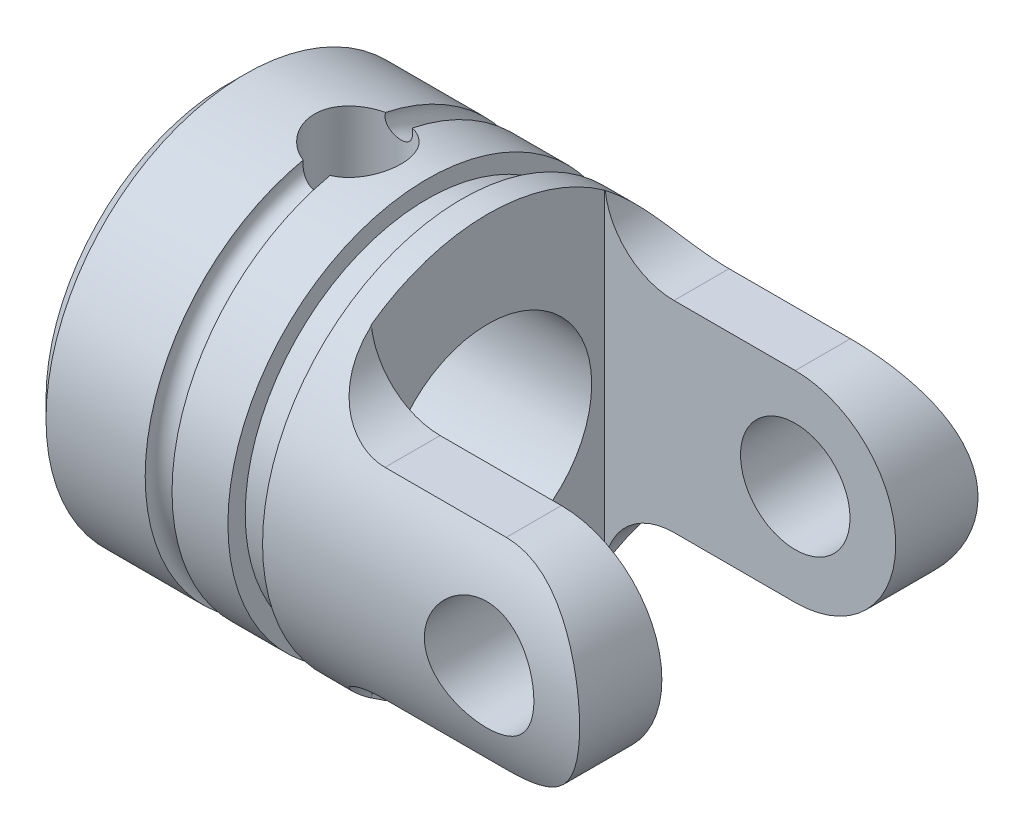
SolidWorks part; units mm, degrees
ref_plane "Front Plane" through (0, 0, 0) normal (0, 0, 1) x (1, 0, 0)
ref_plane "Top Plane" through (0, 0, 0) normal (0, 1, 0) x (1, 0, 0)
ref_plane "Right Plane" through (0, 0, 0) normal (1, 0, 0) x (0, 0, -1)
ref_plane "Plane1" through (0, 0, 0) normal (0, 0, 1) x (1, 0, 0)
sketch "Sketch1" plane through (0, 0, 0) normal (0, 0, 1) x (1, 0, 0)
  line L0 (0, 10.5) -> (0, 7)
  line L1 (0, 7) -> (1, 6)
  line L2 (1, 6) -> (31.8, 6)
  line L3 (31.8, 6) -> (31.8, 11.5)
  line L4 (31.8, 11.5) -> (13.5, 11.5)
  line L5 (13.5, 11.5) -> (13.5, 10.5)
  line L6 (13.5, 10.5) -> (11.5, 10.5)
  line L7 (11.5, 10.5) -> (11.5, 11.5)
  line L8 (11.5, 11.5) -> (8.2746, 11.5)
  line L9 (6.7254, 11.5) -> (1, 11.5)
  line L10 (1, 11.5) -> (0, 10.5)
  line L11 (31.8, 0) -> (0, 0) construction
  arc A0 (8.2746, 11.5) -> (6.7254, 11.5) centre (7.5, 11.3) cw
revolve "Revolve1" add sketch "Sketch1" angle 360 about L11 reverse direction yes
ref_plane "Plane2" through (0, 0, 0) normal (0, 0, 1) x (1, 0, 0)
sketch "Sketch2" plane through (0, 0, 0) normal (0, 0, 1) x (1, 0, 0)
  line L0 (15, 12.5) -> (15, 9.8)
  line L1 (19, 5.8) -> (26, 5.8)
  line L2 (26, -5.8) -> (19, -5.8)
  line L3 (15, -9.8) -> (15, -12.5)
  line L4 (15, -12.5) -> (41, -12.5)
  line L5 (41, -12.5) -> (41, 12.5)
  line L6 (41, 12.5) -> (15, 12.5)
  arc A0 (15, 9.8) -> (19, 5.8) centre (19, 9.8) ccw
  arc A1 (26, 5.8) -> (26, -5.8) centre (26, 0) cw
  arc A2 (19, -5.8) -> (15, -9.8) centre (19, -9.8) ccw
extrude "Cut-Extrude1" cut sketch "Sketch2" against normal blind 23 and the other way blind 23
ref_plane "Plane3" through (0, 0, 0) normal (0, 1, 0) x (1, 0, 0)
sketch "Sketch3" plane through (0, 0, 0) normal (0, 1, 0) x (1, 0, 0)
  line L0 (15, 6.75) -> (15, -6.75)
  line L1 (15, -6.75) -> (41, -6.75)
  line L2 (41, -6.75) -> (41, 6.75)
  line L3 (41, 6.75) -> (15, 6.75)
extrude "Cut-Extrude2" cut sketch "Sketch3" against normal blind 23 and the other way blind 23
ref_plane "Plane4" through (26, 0, 0) normal (1, 0, 0) x (0, 0, -1)
sketch "Sketch4" plane through (26, 0, 0) normal (1, 0, 0) x (0, 0, -1)
  line L0 (-11.5, 0) -> (-11.5, 3.16)
  line L1 (-11.5, 3.16) -> (11.5, 3.16)
  line L2 (11.5, 3.16) -> (11.5, 0)
  line L3 (11.5, 0) -> (-11.5, 0)
  line L4 (11.5, 0) -> (-11.5, 0) construction
revolve "Cut-Revolve1" cut sketch "Sketch4" angle 360 about L4 reverse direction yes
ref_plane "Plane5" through (7.5, 0, 0) normal (1, 0, 0) x (0, 0, -1)
sketch "Sketch5" plane through (7.5, 0, 0) normal (1, 0, 0) x (0, 0, -1)
  line L0 (0, 11.5) -> (2.5, 11.5)
  line L1 (2.5, 11.5) -> (2.5, -11.5)
  line L2 (2.5, -11.5) -> (0, -11.5)
  line L3 (0, -11.5) -> (0, 11.5)
  line L4 (0, -11.5) -> (0, 11.5) construction
revolve "Cut-Revolve2" cut sketch "Sketch5" angle 360 about L4 reverse direction yes
